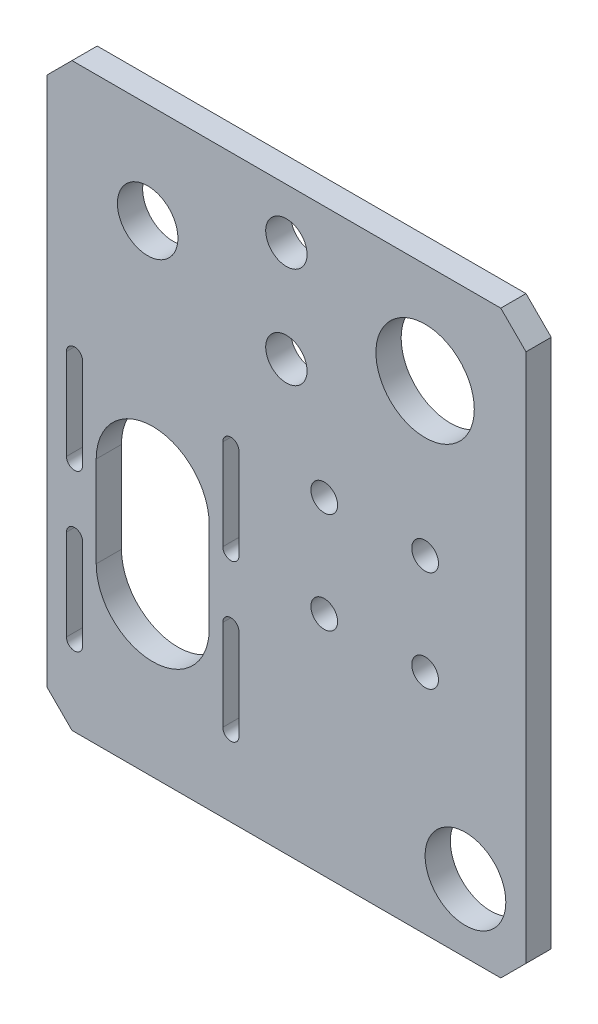
SolidWorks part; units mm, degrees
material "5052-O"
ref_plane "前基準面" through (0, 0, 0) normal (0, 0, 1) x (1, 0, 0)
ref_plane "上基準面" through (0, 0, 0) normal (0, 1, 0) x (1, 0, 0)
ref_plane "右基準面" through (0, 0, 0) normal (1, 0, 0) x (0, 0, -1)
sketch "草圖1" plane through (0, 0, 0) normal (0, 0, 1) x (1, 0, 0)
  line L1 (-47.5, -37.5) -> (47.5, -37.5)
  line L2 (-47.5, -37.5) -> (-47.5, 37.5)
  line L3 (-47.5, 37.5) -> (47.5, 37.5)
  line L4 (47.5, -37.5) -> (47.5, 37.5)
  line L5 (-47.5, -37.5) -> (47.5, 37.5) construction
  line L6 (-47.5, 37.5) -> (47.5, -37.5) construction
  point P0 (0, 0)
  dimension "D1" = 95
  dimension "D2" = 75
extrude "填料-伸長1" add sketch "草圖1" along normal blind 5
hole_wizard "M5 餘隙孔1" positions "草圖2" profile "草圖3" hole size "M5" standard "Ansi Metric" end condition through all
sketch "草圖2" plane through (0, 0, 5) normal (0, 0, 1) x (1, 0, 0)
  line L3 (7.5, 7.5) -> (27.5, 7.5) construction
  line L4 (7.5, 7.5) -> (7.5, 27.5) construction
  line L5 (7.5, 27.5) -> (27.5, 27.5) construction
  line L6 (27.5, 7.5) -> (27.5, 27.5) construction
  line L7 (7.5, 7.5) -> (27.5, 27.5) construction
  line L8 (7.5, 27.5) -> (27.5, 7.5) construction
  line L11 (47.5, 37.5) -> (-47.5, 37.5) construction
  line L12 (47.5, -37.5) -> (47.5, 37.5) construction
  point P6 (27.5, 27.5)
  point P15 (7.5, 7.5)
  point P16 (7.5, 27.5)
  point P17 (27.5, 7.5)
  point P35 (17.5, 17.5)
  dimension "D1" = 20
  dimension "D2" = 20
  dimension "D3" = 20
  dimension "D4" = 20
sketch "草圖3" plane through (27.5, 27.5, 5) normal (1, 0, 0) x (0, -1, 0)
  line L0 (0, 0) -> (0, 5)
  line L1 (0, 5) -> (2.65, 5)
  line L2 (2.65, 5) -> (2.65, 0)
  line L5 (2.65, 0) -> (0, 0)
  line L11 (0, -6.35) -> (0, 107.95) construction
  dimension "貫穿孔直徑" = 5.3
  dimension "貫穿孔深度" = 5
sketch "草圖6" plane through (0, 0, 5) normal (0, 0, 1) x (1, 0, 0)
  line L0 (47.5, 37.5) -> (-47.5, 37.5) construction
  line L2 (-26.5, -6.5) -> (-26.5, 11.5) construction
  line L3 (-37.7, -6.5) -> (-37.7, 11.5)
  line L4 (-15.3, -6.5) -> (-15.3, 11.5)
  line L6 (-42, 27) -> (-42, 9) construction
  line L7 (-42, -4) -> (-11, -4) construction
  line L8 (-42, -4) -> (-42, 27) construction
  line L9 (-42, 27) -> (-11, 27) construction
  line L10 (-11, -4) -> (-11, 27) construction
  line L11 (-42, -4) -> (-11, 27) construction
  line L12 (-42, 27) -> (-11, -4) construction
  line L13 (-40.4, 27) -> (-40.4, 9)
  line L14 (-43.6, 27) -> (-43.6, 9)
  line L15 (-11, 27) -> (-11, 9) construction
  line L16 (-9.4, 27) -> (-9.4, 9)
  line L17 (-12.6, 27) -> (-12.6, 9)
  line L18 (-11, -4) -> (-11, -22) construction
  line L19 (-9.4, -4) -> (-9.4, -22)
  line L20 (-12.6, -4) -> (-12.6, -22)
  line L21 (-42, -4) -> (-42, -22) construction
  line L22 (-40.4, -4) -> (-40.4, -22)
  line L23 (-43.6, -4) -> (-43.6, -22)
  line L25 (-47.5, 37.5) -> (-47.5, -37.5) construction
  arc A0 (-37.7, -6.5) -> (-15.3, -6.5) centre (-26.5, -6.5) ccw
  arc A1 (-15.3, 11.5) -> (-37.7, 11.5) centre (-26.5, 11.5) ccw
  arc A2 (-40.4, 27) -> (-43.6, 27) centre (-42, 27) ccw
  arc A3 (-43.6, 9) -> (-40.4, 9) centre (-42, 9) ccw
  arc A4 (-9.4, 27) -> (-12.6, 27) centre (-11, 27) ccw
  arc A5 (-12.6, 9) -> (-9.4, 9) centre (-11, 9) ccw
  arc A6 (-9.4, -4) -> (-12.6, -4) centre (-11, -4) ccw
  arc A7 (-12.6, -22) -> (-9.4, -22) centre (-11, -22) ccw
  arc A8 (-40.4, -4) -> (-43.6, -4) centre (-42, -4) ccw
  arc A9 (-43.6, -22) -> (-40.4, -22) centre (-42, -22) ccw
  point P6 (-26.5, 2.5)
  point P13 (-26.5, 11.5)
  point P18 (-42, 18)
  point P24 (-11, 18)
  point P30 (-11, -13)
  point P36 (-42, -13)
  dimension "D3" = 11.2
  dimension "D7" = 1.6
  dimension "D1" = 18
  dimension "D2" = 21
  dimension "D4" = 35
  dimension "D5" = 31
  dimension "D6" = 31
extrude "除料-伸長2" cut sketch "草圖6" against normal through all
sketch "草圖4" plane through (0, 0, 5) normal (0, 0, 1) x (1, 0, 0)
  circle A0 centre (35.5, -24) radius 8
  circle A1 centre (27.5, 7.5) radius 2.65 construction
  dimension "D3" = 16
  dimension "D1" = 31.5
  dimension "D2" = 8
extrude "除料-伸長3" cut sketch "草圖4" against normal up to next
sketch "草圖7" plane through (0, 37.5, 0) normal (0, 1, 0) x (1, 0, 0)
  line L1 (47.5, 0) -> (-47.5, 0)
  line L2 (47.5, 0) -> (47.5, -5)
  line L3 (47.5, -5) -> (-47.5, -5)
  line L4 (-47.5, 0) -> (-47.5, -5)
extrude "填料-伸長2" add sketch "草圖7" along normal blind 40
sketch "草圖8" plane through (0, 0, 5) normal (0, 0, 1) x (1, 0, 0)
  line L0 (47.5, -37.5) -> (47.5, 77.5) construction
  line L1 (-47.5, 77.5) -> (47.5, 77.5) construction
  circle A0 centre (27.5, 57.5) radius 9.75
  dimension "D1" = 19.5
  dimension "D3" = 20
  dimension "D2" = 20
extrude "除料-伸長4" cut sketch "草圖8" against normal up to next
sketch "草圖9" plane through (0, 0, 5) normal (0, 0, 1) x (1, 0, 0)
  line L0 (-47.5, 77.5) -> (47.5, 77.5) construction
  circle A0 centre (0, 67.5) radius 4.1
  circle A1 centre (0, 47.5) radius 4.1
  point P6 (0, 0)
  point P8 (-8.5806, 67.5)
  dimension "D1" = 8.2
  dimension "D2" = 8.2
  dimension "D4" = 10
  dimension "D3" = 20
extrude "除料-伸長5" cut sketch "草圖9" against normal up to next
sketch "草圖10" plane through (0, 0, 5) normal (0, 0, 1) x (1, 0, 0)
  line L0 (-47.5, 77.5) -> (47.5, 77.5) construction
  line L1 (-47.5, 77.5) -> (-47.5, -37.5) construction
  circle A0 centre (-27.5, 57.5) radius 6
  dimension "D1" = 12
  dimension "D3" = 20
  dimension "D2" = 20
extrude "除料-伸長6" cut sketch "草圖10" against normal up to next
chamfer "導角2" distance 5 angle 45 4 edges at (-47.5, -37.5, 2.5) (47.5, -37.5, 2.5) (-47.5, 77.5, 2.5) (47.5, 77.5, 2.5)
